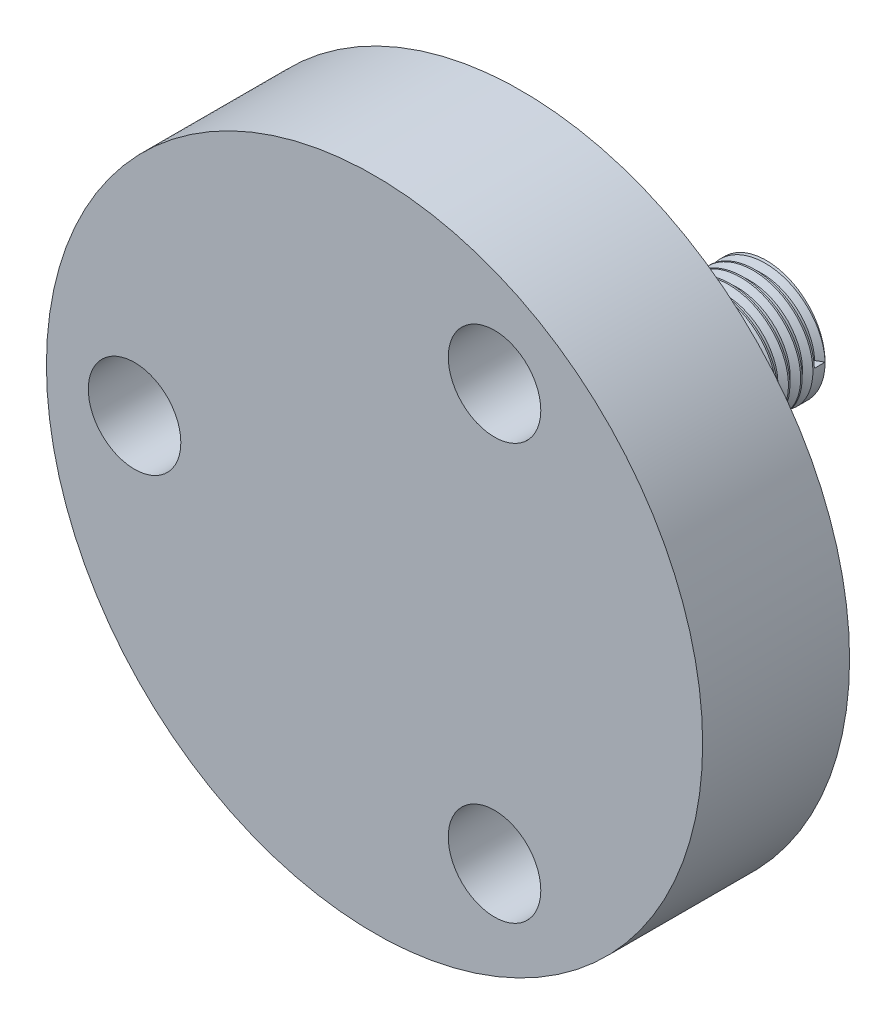
SolidWorks part; units mm, degrees
ref_plane "Front Plane" through (0, 0, 0) normal (0, 0, 1) x (1, 0, 0)
ref_plane "Top Plane" through (0, 0, 0) normal (0, 1, 0) x (1, 0, 0)
ref_plane "Right Plane" through (0, 0, 0) normal (1, 0, 0) x (0, 0, -1)
sketch "Sketch2" plane through (0, 0, 0) normal (0, 0, 1) x (1, 0, 0)
  circle A0 centre (0, 0) radius 8.509
  dimension "D1" = 17.018
extrude "Boss-Extrude1" add sketch "Sketch2" along normal blind 3.81
ref_plane "Plane1" through (0, 0, 3.81) normal (0, 0, 1) x (1, 0, 0)
sketch "Sketch3" plane through (0, 0, 3.81) normal (0, 0, 1) x (1, 0, 0)
  line L0 (-8.509, 0) -> (8.509, 0) construction
  circle A0 centre (0, 0) radius 6.223 construction
  circle A2 centre (0, 0) radius 8.509 construction
  circle A3 centre (-6.223, 0) radius 1.143
  circle A4 centre (3.1115, 5.3893) radius 1.143
  circle A5 centre (3.1115, -5.3893) radius 1.143
  point P16 (0, 0)
  dimension "D1" = 12.446
  dimension "D2" = 2.286
  dimension "D4" = 5.3893
  dimension "D5" = 3.1115
  dimension "D3" = 3
hole_wizard "M2 Clearance Hole1" positions "Sketch6" profile "Sketch7" hole size "M2" standard "ANSI Metric" end condition through all
sketch "Sketch6" plane through (0, 0, 3.81) normal (0, 0, 1) x (1, 0, 0)
  point P0 (-6.223, 0)
  point P3 (3.1115, 5.3893)
  point P6 (3.1115, -5.3893)
sketch "Sketch7" plane through (-6.223, 0, 3.81) normal (1, 0, 0) x (0, -1, 0)
  line L0 (0, 0) -> (0, 3.81)
  line L1 (0, 3.81) -> (1.2, 3.81)
  line L2 (1.2, 3.81) -> (1.2, 0)
  line L5 (1.2, 0) -> (0, 0)
  line L11 (0, -6.35) -> (0, 107.95) construction
  dimension "Thru Hole Dia." = 2.4
  dimension "Thru Hole Depth" = 3.81
sketch "Sketch8" plane through (0, 0, 0) normal (0, 0, -1) x (-1, 0, 0)
  circle A1 centre (0, 0) radius 1.524
  point P0 (0, 0)
  dimension "D1" = 3.048
extrude "Boss-Extrude2" add sketch "Sketch8" along normal blind 6.35
thread "Thread1" pitch 0.3175 method cut profile "Thread Profile2" start angle 0, offset 0, length 0, pitch 0.3175, diameter 3.048
ref_plane "Plane3" through (1.524, 0, -6.35) normal (0, -1, 0) x (1, 0, 0)
sketch "Thread Profile2" plane through (1.524, 0, -6.35) normal (0, -1, 0) x (1, 0, 0)
  line L0 (0, 0) -> (0, 0.3175) construction
  line L11 (0, 0) -> (0, 0.2778)
  line L12 (0, 0.2778) -> (-0.1719, 0.1786)
  line L13 (-0.1719, 0.1786) -> (-0.1719, 0.0992)
  line L15 (-0.1719, 0.0992) -> (0, 0)
  line L17 (-0.1719, 0.1389) -> (0, 0.1389) construction
  point P2 (0, 0)
  dimension "Pitch" = 0.3175
  dimension "Profile_Angle" = 60
  dimension "Profile_Land" = 0.0794
  dimension "Profile_Height" = 0.1719
